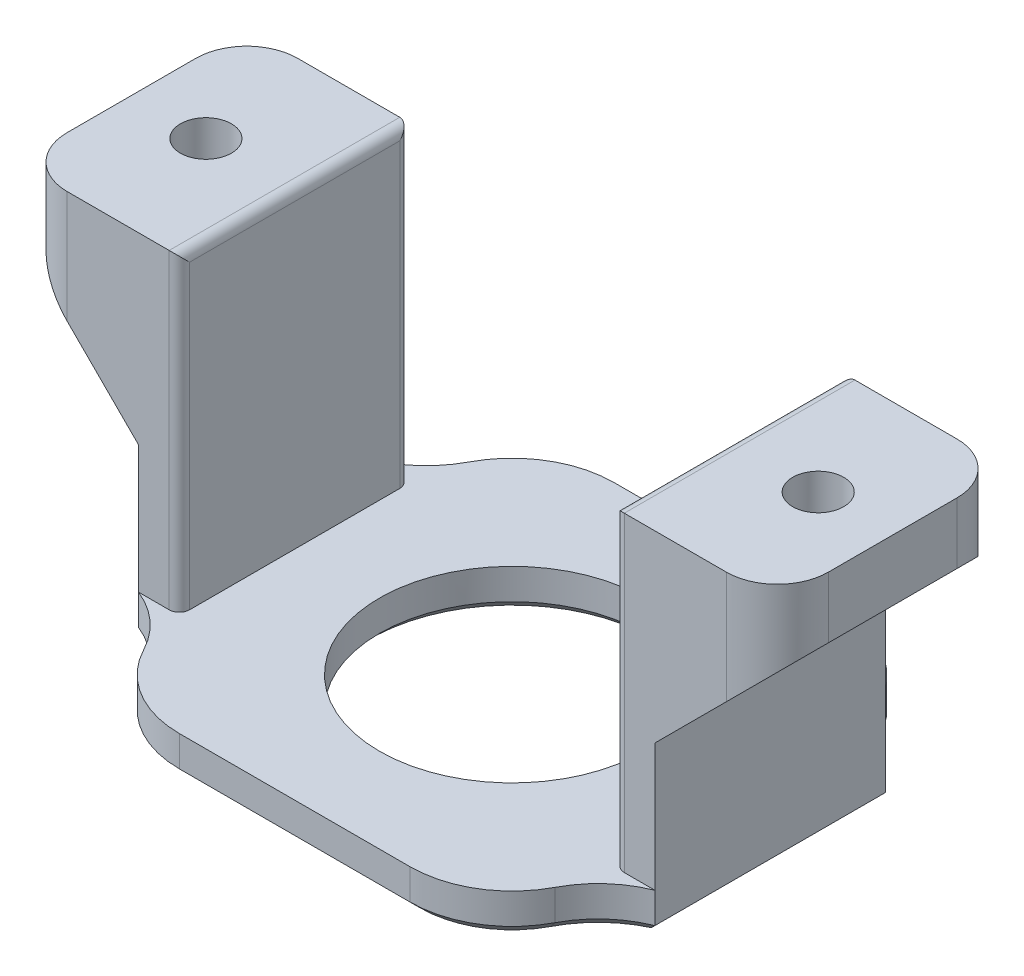
SolidWorks part; units mm, degrees
ref_plane "Спереди" through (0, 0, 0) normal (0, 0, 1) x (1, 0, 0)
ref_plane "Сверху" through (0, 0, 0) normal (0, 1, 0) x (1, 0, 0)
ref_plane "Справа" through (0, 0, 0) normal (1, 0, 0) x (0, 0, -1)
sketch "Эскиз1" plane through (0, 0, 0) normal (0, 1, 0) x (1, 0, 0)
  line L1 (-21.3, -21.3) -> (21.3, -21.3)
  line L2 (-21.3, -21.3) -> (-21.3, 21.3)
  line L3 (-21.3, 21.3) -> (21.3, 21.3)
  line L4 (21.3, -21.3) -> (21.3, 21.3)
  line L5 (0, 21.3) -> (0, -21.3) construction
  line L6 (-21.3, 0) -> (21.3, 0) construction
  point P0 (0, 0)
  dimension "D1" = 42.6
extrude "Бобышка-Вытянуть1" add sketch "Эскиз1" along normal blind 4
sketch "Эскиз2" plane through (0, 4, 0) normal (0, 1, 0) x (1, 0, 0)
  circle A0 centre (0, 0) radius 13
  dimension "D1" = 26
extrude "Вырез-Вытянуть1" cut sketch "Эскиз2" against normal blind 6
fillet "Скругление1" radius 10 4 edges at (-21.3, 2, -21.3) (-21.3, 2, 21.3) (21.3, 2, -21.3) (21.3, 2, 21.3)
sketch "Эскиз3" plane through (0, 0, 0) normal (0, 1, 0) x (1, 0, 0)
  line L0 (0, 22.9171) -> (0, 0) construction
  line L1 (0, 0) -> (35.9414, 0) construction
  line L2 (-25.3, 11.3) -> (-21.3, 11.3)
  line L3 (25.3, -11.3) -> (21.3, -11.3)
  line L4 (25.3, -11.3) -> (25.3, 11.3)
  line L5 (25.3, 11.3) -> (21.3, 11.3)
  line L6 (21.3, -11.3) -> (21.3, 11.3)
  line L7 (23.3, 11.3) -> (23.3, -11.3) construction
  line L8 (25.3, 0) -> (21.3, 0) construction
  line L9 (-21.3, -11.3) -> (-21.3, 11.3)
  line L10 (-25.3, -11.3) -> (-21.3, -11.3)
  line L11 (-25.3, -11.3) -> (-25.3, 11.3)
  point P3 (23.3, 0)
  dimension "D1" = 4
extrude "Бобышка-Вытянуть2" add sketch "Эскиз3" along normal blind 34.5
fillet "Скругление2" radius 10 4 edges at (21.3, 2, -11.3) (-21.3, 2, -11.3) (-21.3, 2, 11.3) (21.3, 2, 11.3)
sketch "Эскиз4" plane through (0, 34.5, 0) normal (0, 1, 0) x (1, 0, 0)
  line L0 (0, 22.7747) -> (0, 0) construction
  line L1 (0, 0) -> (36.6531, 0) construction
  line L2 (-37.3, 11.3) -> (-25.3, 11.3)
  line L3 (37.3, -11.3) -> (25.3, -11.3)
  line L4 (37.3, -11.3) -> (37.3, 11.3)
  line L5 (37.3, 11.3) -> (25.3, 11.3)
  line L6 (25.3, -11.3) -> (25.3, 11.3)
  line L7 (31.3, 11.3) -> (31.3, -11.3) construction
  line L8 (37.3, 0) -> (25.3, 0) construction
  line L9 (-25.3, -11.3) -> (-25.3, 11.3)
  line L10 (-37.3, -11.3) -> (-25.3, -11.3)
  line L11 (-37.3, -11.3) -> (-37.3, 11.3)
  point P4 (31.3, 0)
  dimension "D1" = 12
extrude "Бобышка-Вытянуть3" add sketch "Эскиз4" against normal blind 6
fillet "Скругление3" radius 5 4 edges at (37.3, 31.5, 11.3) (37.3, 31.5, -11.3) (-37.3, 31.5, -11.3) (-37.3, 31.5, 11.3)
fillet "Скругление4" radius 1 6 edges at (-21.3, 19.25, -11.3) (-21.3, 34.5, 0) (-21.3, 19.25, 11.3) (21.3, 34.5, 0) (21.3, 19.25, -11.3) (21.3, 19.25, 11.3)
chamfer "Фаска3" distance 1 angle 45 13 edges at (0, 0, 21.3) (16.4758, 0, 19.8564) (22.3137, 0, 13.1615) (25.3, 0, 0) (22.3137, 0, -13.1615) (16.4758, 0, -19.8564) (0, 0, -21.3) (-16.4758, 0, -19.8564) (-22.3137, 0, -13.1615) (-25.3, 0, 0) (-22.3137, 0, 13.1615) (-16.4758, 0, 19.8564) (0, 0, -13)
sketch "Эскиз5" plane through (0, 34.5, 0) normal (0, 1, 0) x (1, 0, 0)
  line L0 (0, 26.1185) -> (0, 0) construction
  line L1 (0, 0) -> (48.3269, 0) construction
  circle A0 centre (30, 0) radius 2.5
  circle A1 centre (-30, 0) radius 2.5
  dimension "D1" = 30
extrude "Вырез-Вытянуть2" cut sketch "Эскиз5" against normal through all
chamfer "Фаска4" distance 12 angle 45 2 edges at (-25.3, 28.5, 0) (25.3, 28.5, 0)
sketch "Эскиз6" plane through (0, 0, 0) normal (0, -1, 0) x (1, 0, 0)
  line L0 (0, 27.5439) -> (0, 0) construction
  line L1 (0, 0) -> (51.4858, 0) construction
  circle A0 centre (30, 0) radius 4.2
  circle A1 centre (-30, 0) radius 4.2
  dimension "D1" = 8.4
  dimension "D2" = 30
extrude "Вырез-Вытянуть5" cut sketch "Эскиз6" against normal blind 28
chamfer "Фаска5" distance 2 angle 45 2 edges at (30, 28, -2.5) (-30, 28, 2.5)
